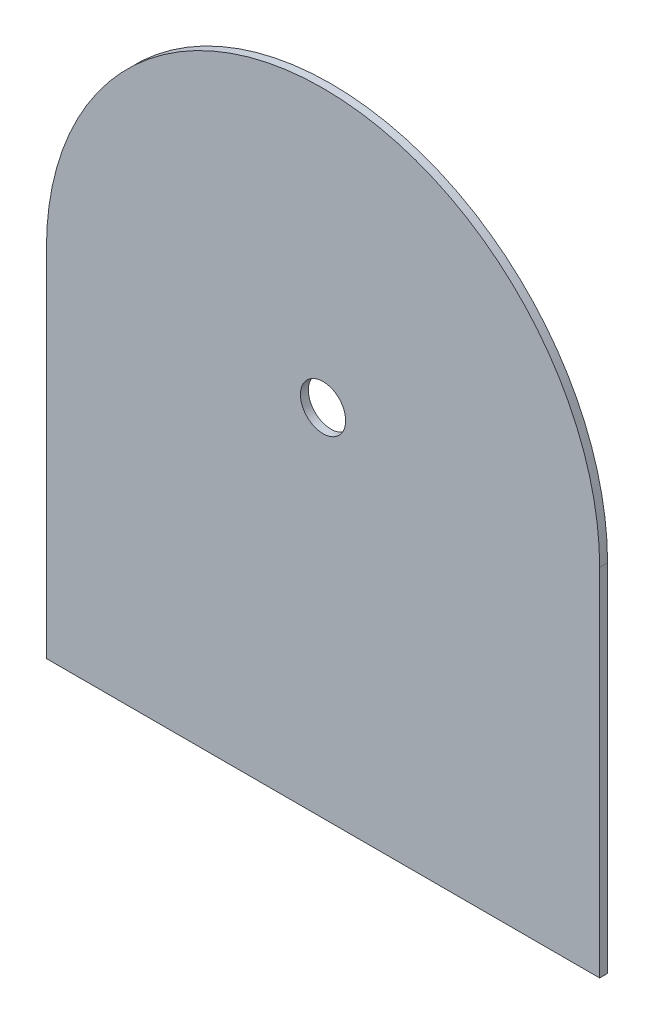
SolidWorks part; units mm, degrees
material "201 Annealed Stainless Steel (SS)"
ref_plane "Front Plane" through (0, 0, 0) normal (0, 0, 1) x (1, 0, 0)
ref_plane "Top Plane" through (0, 0, 0) normal (0, 1, 0) x (1, 0, 0)
ref_plane "Right Plane" through (0, 0, 0) normal (1, 0, 0) x (0, 0, -1)
sketch "Plate shape" plane through (0, 0, 0) normal (0, 0, 1) x (1, 0, 0)
  line L3 (0, 50) -> (175, 50) construction
  line L4 (0, 225) -> (-175, 225) construction
  line L5 (0, 225) -> (175, 225) construction
  line L7 (-175, 225) -> (-175, 0)
  line L8 (-175, 0) -> (175, 0)
  line L9 (0, 225) -> (0, 0) construction
  line L10 (175, 225) -> (175, 0)
  arc A0 (-175, 225) -> (175, 225) centre (0, 225) cw
  arc A1 (175, 225) -> (-175, 225) centre (0, 225) cw construction
  point P2 (175, 50)
  point P4 (0, 0)
  dimension "D1" = 175
  dimension "D2" = 50
  dimension "D3" = 350
extrude "Outer casing" add sketch "Plate shape" along normal blind 5
sketch "Sketch1" plane through (0, 0, 5) normal (0, 0, 1) x (1, 0, 0)
  circle A0 centre (0, 225) radius 175 construction
  arc A1 (175, 225) -> (-175, 225) centre (0, 225) ccw construction
  circle A2 centre (0, 225) radius 14.3
  dimension "D1" = 28.6
extrude "Inner Cutout" cut sketch "Sketch1" against normal blind 10
sketch "Sketch2" plane through (0, 0, 0) normal (1, 0, 0) x (0, 0, -1)
  line L0 (-5, 210.7) -> (0, 210.7) construction
  point P3 (-2.5, 210.7)
  point P4 (-2.5, 210.7)
ref_plane "Plane1" through (0, 0, 2.5) normal (0, 0, 1) x (1, 0, 0)
sketch "Sketch3" plane through (0, 0, 2.5) normal (0, 0, 1) x (1, 0, 0)
  circle A0 centre (0, 225) radius 14.3 construction
  circle A1 centre (0, 225) radius 14.3 construction
